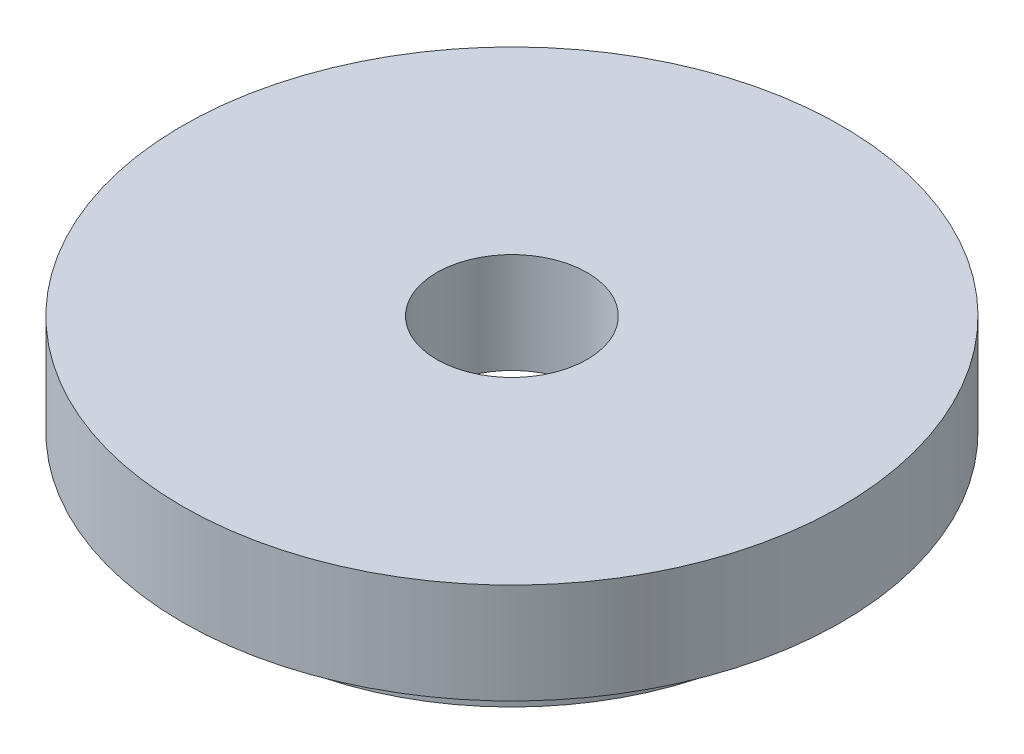
SolidWorks part; units mm, degrees
ref_plane "Front Plane" through (0, 0, 0) normal (0, 0, 1) x (1, 0, 0)
ref_plane "Top Plane" through (0, 0, 0) normal (0, 1, 0) x (1, 0, 0)
ref_plane "Right Plane" through (0, 0, 0) normal (1, 0, 0) x (0, 0, -1)
sketch "Sketch1" plane through (0, 0, 0) normal (0, 1, 0) x (1, 0, 0)
  circle A0 centre (0, 0) radius 19.7
  dimension "D1" = 39.4
extrude "Boss-Extrude1" add sketch "Sketch1" along normal blind 6
sketch "Sketch2" plane through (0, 0, 0) normal (0, 1, 0) x (1, 0, 0)
  circle A0 centre (0, 0) radius 11.9
  circle A1 centre (0, 0) radius 15.9
  dimension "D1" = 4
  dimension "D2" = 23.8
extrude "Boss-Extrude2" add sketch "Sketch2" against normal blind 3
sketch "Sketch4" plane through (0, 0, 0) normal (0, -1, 0) x (1, 0, 0)
  line L0 (3.3, 0) -> (-3.3, 0) construction
  circle A0 centre (0, 0) radius 4.5
  circle A2 centre (0, 0) radius 11.9 construction
extrude "Cut-Extrude2" cut sketch "Sketch4" against normal up to surface (6 mm away) up to face at (0, 6, 19.7)
sketch "Sketch3" plane through (0, -3, 0) normal (0, -1, 0) x (1, 0, 0)
  line L0 (4.95, 0) -> (-4.95, 0) construction
  line L1 (25.1105, -3) -> (9.1701, -3)
  line L2 (25.1105, -3) -> (25.1105, 3)
  line L3 (25.1105, 3) -> (9.1701, 3)
  line L4 (9.1701, -3) -> (9.1701, 3)
  line L5 (25.1105, -3) -> (9.1701, 3) construction
  line L6 (25.1105, 3) -> (9.1701, -3) construction
  point P0 (17.1403, 0)
  dimension "D1" = 6
extrude "Cut-Extrude1" cut sketch "Sketch3" against normal blind 3
